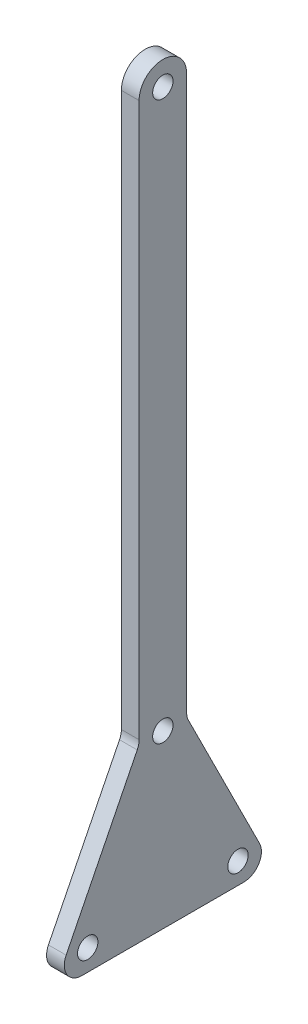
SolidWorks part; units mm, degrees
ref_plane "Front Plane" through (0, 0, 0) normal (0, 0, 1) x (1, 0, 0)
ref_plane "Top Plane" through (0, 0, 0) normal (0, 1, 0) x (1, 0, 0)
ref_plane "Right Plane" through (0, 0, 0) normal (1, 0, 0) x (0, 0, -1)
sketch "Sketch1" plane through (0, 0, 0) normal (1, 0, 0) x (0, 0, -1)
  line L0 (-13.4747, 0) -> (13.4747, 0) construction
  line L1 (0, 0) -> (0, 26.9494) construction
  line L2 (-13.4747, 0) -> (0, 26.9494) construction
  line L3 (0, 26.9494) -> (13.4747, 0) construction
  line L4 (13.4747, 0) -> (-13.4747, 0) construction
  line L5 (19.6394, -3.81) -> (-19.6394, -3.81)
  line L6 (-19.6394, -3.81) -> (0, 35.4688)
  line L7 (0, 35.4688) -> (19.6394, -3.81)
  line L8 (0, 26.9494) -> (0, 126.9494) construction
  line L9 (0, 126.9494) -> (0, 26.9494) construction
  line L10 (4.2597, 126.9494) -> (4.2597, 26.9494)
  line L11 (-4.2597, 126.9494) -> (-4.2597, 26.9494)
  circle A0 centre (-13.4747, 0) radius 1.8288
  circle A1 centre (0, 26.9494) radius 1.8288
  circle A2 centre (13.4747, 0) radius 1.8288
  circle A3 centre (0, 126.9494) radius 1.8288
  arc A4 (4.2597, 126.9494) -> (-4.2597, 126.9494) centre (0, 126.9494) ccw
  arc A5 (-4.2597, 26.9494) -> (4.2597, 26.9494) centre (0, 26.9494) ccw
  point P4 (0, 0)
  point P14 (0, 76.9494)
  dimension "D3" = 3.6576
  dimension "D1" = 26.9494
  dimension "D5" = 100
  dimension "D2" = 3.81
extrude "Boss-Extrude1" add sketch "Sketch1" along normal blind 3.175 contours A5 L6 L5 L7 A2 A0 | L6 A5 L7 A1 | L10 A4 L11 L6 L7 A3 region at (0, 7.8228, 0) region at (0, 22.8433, 0) region at (0, 80.1435, 0)
fillet "Fillet1" radius 3.175 4 edges at (1.5875, -3.81, -19.6394) (1.5875, -3.81, 19.6394) (1.5875, 26.9494, 4.2597) (1.5875, 26.9494, -4.2597)
